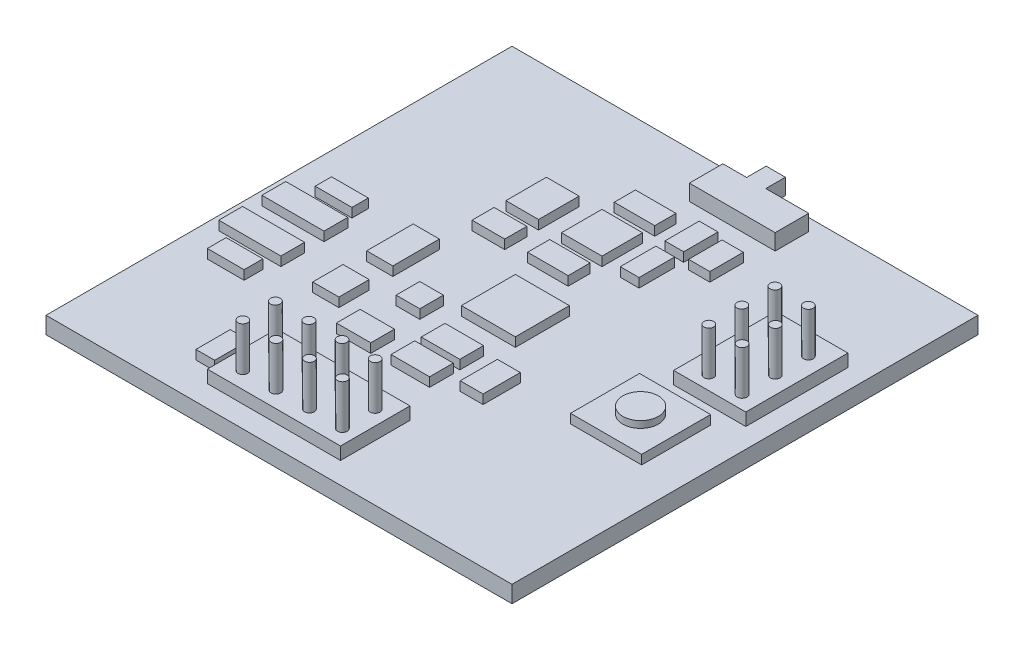
SolidWorks part; units mm, degrees
ref_plane "Front Plane" through (0, 0, 0) normal (0, 0, 1) x (1, 0, 0)
ref_plane "Top Plane" through (0, 0, 0) normal (0, 1, 0) x (1, 0, 0)
ref_plane "Right Plane" through (0, 0, 0) normal (1, 0, 0) x (0, 0, -1)
sketch "Sketch1" plane through (0, 0, 0) normal (0, 1, 0) x (1, 0, 0)
  line L1 (0, 0) -> (35.052, 0)
  line L2 (0, 0) -> (0, 35.052)
  line L3 (0, 35.052) -> (35.052, 35.052)
  line L4 (35.052, 0) -> (35.052, 35.052)
extrude "Boss-Extrude1" add sketch "Sketch1" along normal blind 1.27
sketch "Sketch2" plane through (0, 1.27, 0) normal (0, 1, 0) x (1, 0, 0)
  line L1 (12.548, 13.7882) -> (14.326, 13.7882)
  line L2 (12.548, 13.7882) -> (12.548, 15.5662)
  line L3 (12.548, 15.5662) -> (14.326, 15.5662)
  line L4 (14.326, 13.7882) -> (14.326, 15.5662)
  line L5 (15.6823, 15.5583) -> (19.7463, 15.5583)
  line L6 (15.6823, 15.5583) -> (15.6823, 19.6223)
  line L7 (15.6823, 19.6223) -> (19.7463, 19.6223)
  line L8 (19.7463, 15.5583) -> (19.7463, 19.6223)
  line L9 (14.699, 24.072) -> (17.747, 24.072)
  line L10 (14.699, 24.072) -> (14.699, 27.12)
  line L11 (14.699, 27.12) -> (17.747, 27.12)
  line L12 (17.747, 24.072) -> (17.747, 27.12)
  line L13 (16.7885, 31.6063) -> (23.2414, 31.6063)
  line L14 (16.7885, 31.6063) -> (16.7885, 34.126)
  line L15 (16.7885, 34.126) -> (23.2414, 34.126)
  line L16 (23.2414, 31.6063) -> (23.2414, 34.126)
  line L17 (18.5708, 34.126) -> (20.015, 34.126)
  line L18 (18.5708, 34.126) -> (18.5708, 35.601)
  line L19 (18.5708, 35.601) -> (20.015, 35.601)
  line L20 (20.015, 34.126) -> (20.015, 35.601)
  line L21 (10.52, 27.12) -> (12.9782, 27.12)
  line L22 (10.52, 27.12) -> (10.52, 24.072)
  line L23 (10.52, 24.072) -> (12.9782, 24.072)
  line L24 (12.9782, 27.12) -> (12.9782, 24.072)
  line L25 (14.699, 29.6397) -> (17.747, 29.6397)
  line L26 (14.699, 29.6397) -> (14.699, 28.0419)
  line L27 (14.699, 28.0419) -> (17.747, 28.0419)
  line L28 (17.747, 29.6397) -> (17.747, 28.0419)
  line L29 (21.2134, 29.6397) -> (22.8113, 29.6397)
  line L30 (21.2134, 29.6397) -> (21.2134, 27.12)
  line L31 (21.2134, 27.12) -> (22.8113, 27.12)
  line L32 (22.8113, 29.6397) -> (22.8113, 27.12)
  line L33 (19.1239, 30.0085) -> (20.5374, 30.0085)
  line L34 (19.1239, 30.0085) -> (19.1239, 27.4273)
  line L35 (19.1239, 27.4273) -> (20.5374, 27.4273)
  line L36 (20.5374, 30.0085) -> (20.5374, 27.4273)
  line L37 (19.1239, 26.7513) -> (20.5374, 26.7513)
  line L38 (19.1239, 26.7513) -> (19.1239, 24.072)
  line L39 (19.1239, 24.072) -> (20.5374, 24.072)
  line L40 (20.5374, 26.7513) -> (20.5374, 24.072)
  line L41 (10.52, 23.1868) -> (12.9782, 23.1868)
  line L42 (10.52, 23.1868) -> (10.52, 21.5275)
  line L43 (10.52, 21.5275) -> (12.9782, 21.5275)
  line L44 (12.9782, 23.1868) -> (12.9782, 21.5275)
  line L45 (14.699, 23.1868) -> (17.747, 23.1868)
  line L46 (14.699, 23.1868) -> (14.699, 21.5275)
  line L47 (14.699, 21.5275) -> (17.747, 21.5275)
  line L48 (17.747, 23.1868) -> (17.747, 21.5275)
  line L49 (8.5534, 19.0692) -> (10.52, 19.0692)
  line L50 (8.5534, 19.0692) -> (8.5534, 15.5662)
  line L51 (8.5534, 15.5662) -> (10.52, 15.5662)
  line L52 (10.52, 19.0692) -> (10.52, 15.5662)
  line L53 (8.5534, 13.7882) -> (10.52, 13.7882)
  line L54 (8.5534, 13.7882) -> (8.5534, 11.5101)
  line L55 (8.5534, 11.5101) -> (10.52, 11.5101)
  line L56 (10.52, 13.7882) -> (10.52, 11.5101)
  line L57 (12.1178, 11.5101) -> (14.699, 11.5101)
  line L58 (12.1178, 11.5101) -> (12.1178, 9.7279)
  line L59 (12.1178, 9.7279) -> (14.699, 9.7279)
  line L60 (14.699, 11.5101) -> (14.699, 9.7279)
  line L61 (16.223, 13.7882) -> (19.1239, 13.7882)
  line L62 (16.223, 13.7882) -> (16.223, 12.0017)
  line L63 (16.223, 12.0017) -> (19.1239, 12.0017)
  line L64 (19.1239, 13.7882) -> (19.1239, 12.0017)
  line L65 (16.223, 11.5101) -> (19.1239, 11.5101)
  line L66 (16.223, 11.5101) -> (16.223, 9.7279)
  line L67 (16.223, 9.7279) -> (19.1239, 9.7279)
  line L68 (19.1239, 11.5101) -> (19.1239, 9.7279)
  line L69 (20.5374, 13.4152) -> (22.2581, 13.4152)
  line L70 (20.5374, 13.4152) -> (20.5374, 10.619)
  line L71 (20.5374, 10.619) -> (22.2581, 10.619)
  line L72 (22.2581, 13.4152) -> (22.2581, 10.619)
  line L73 (26.8059, 17.8401) -> (32.1526, 17.8401)
  line L74 (26.8059, 17.8401) -> (26.8059, 12.6492)
  line L75 (26.8059, 12.6492) -> (32.1526, 12.6492)
  line L76 (32.1526, 17.8401) -> (32.1526, 12.6492)
  line L77 (0.9942, 17.0412) -> (5.6649, 17.0412)
  line L78 (0.9942, 17.0412) -> (0.9942, 15.2446)
  line L79 (0.9942, 15.2446) -> (5.6649, 15.2446)
  line L80 (5.6649, 17.0412) -> (5.6649, 15.2446)
  line L81 (0.9942, 13.7882) -> (5.6649, 13.7882)
  line L82 (0.9942, 13.7882) -> (0.9942, 12.0017)
  line L83 (0.9942, 12.0017) -> (5.6649, 12.0017)
  line L84 (5.6649, 13.7882) -> (5.6649, 12.0017)
  line L85 (2.4077, 19.0692) -> (5.1733, 19.0692)
  line L86 (2.4077, 19.0692) -> (2.4077, 17.8401)
  line L87 (2.4077, 17.8401) -> (5.1733, 17.8401)
  line L88 (5.1733, 19.0692) -> (5.1733, 17.8401)
  line L89 (2.4077, 11.1414) -> (5.1733, 11.1414)
  line L90 (2.4077, 11.1414) -> (2.4077, 9.7279)
  line L91 (2.4077, 9.7279) -> (5.1733, 9.7279)
  line L92 (5.1733, 11.1414) -> (5.1733, 9.7279)
  line L93 (8.5534, 5.303) -> (9.9669, 5.303)
  line L94 (8.5534, 5.303) -> (8.5534, 2.7218)
  line L95 (8.5534, 2.7218) -> (9.9669, 2.7218)
  line L96 (9.9669, 5.303) -> (9.9669, 2.7218)
  line L97 (28.1416, 26.7513) -> (33.5661, 26.7513)
  line L98 (28.1416, 26.7513) -> (28.1416, 19.0692)
  line L99 (28.1416, 19.0692) -> (33.5661, 19.0692)
  line L100 (33.5661, 26.7513) -> (33.5661, 19.0692)
  line L101 (10.52, 6.8394) -> (20.5374, 6.8394)
  line L102 (10.52, 6.8394) -> (10.52, 1.6156)
  line L103 (10.52, 1.6156) -> (20.5374, 1.6156)
  line L104 (20.5374, 6.8394) -> (20.5374, 1.6156)
  circle A0 centre (29.4793, 15.2446) radius 1.3377
  circle A1 centre (11.9527, 5.303) radius 0.3687
  circle A2 centre (14.4719, 5.303) radius 0.373
  circle A3 centre (16.9634, 5.303) radius 0.3653
  circle A4 centre (19.4549, 5.303) radius 0.3653
  circle A5 centre (19.4688, 2.8252) radius 0.3653
  circle A6 centre (16.9634, 2.8528) radius 0.3653
  circle A7 centre (14.4719, 2.8252) radius 0.3653
  circle A8 centre (11.9527, 2.8528) radius 0.3653
  circle A9 centre (29.7588, 25.0693) radius 0.3653
  circle A10 centre (32.277, 25.0693) radius 0.3653
  circle A11 centre (32.277, 22.5845) radius 0.3653
  circle A12 centre (32.277, 20.083) radius 0.3653
  circle A13 centre (29.7588, 20.0996) radius 0.3653
  circle A14 centre (29.7588, 22.5845) radius 0.3653
  dimension "D1" = 3.048
  dimension "D2" = 3.048
  dimension "D3" = 1.778
  dimension "D4" = 1.778
  dimension "D5" = 4.064
  dimension "D6" = 4.064
extrude "Boss-Extrude2" add sketch "Sketch2" along normal blind 1.1989 separate body contours L15 L16 L13 L14 | L20 L19 L18 L17
extrude "Boss-Extrude3" add sketch "Sketch2<3>" along normal blind 0.6909 contours L28 L25 L26 L27 region at (16.223, 1.27, -28.8408)
sketch "Sketch2<3>" plane through (0, 1.27, 0) normal (0, 1, 0) x (1, 0, 0) same geometry as "Sketch2"
extrude "Boss-Extrude4" add sketch "Sketch2<4>" along normal blind 0.6909 contours L36 L33 L34 L35 | L32 L29 L30 L31 | L40 L37 L38 L39 | L48 L45 L46 L47 | L24 L21 L22 L23 | L9 L12 L11 L10 | L5 L8 L7 L6 | L68 L65 L66 L67 | L72 L69 L70 L71 | L60 L57 L58 L59 | L56 L53 L54 L55 | L52 L49 L50 L51 | L80 L77 L78 L79 | L84 L81 L82 L83 | L92 L89 L90 L91 | L96 L93 L94 L95 | L41 L44 L43 L42 | L61 L64 L63 L62 | L3 L4 L1 L2 | L85 L88 L87 L86 region at (17.7143, 1.27, -17.5903) region at (16.223, 1.27, -25.596) region at (11.7491, 1.27, -25.596) region at (22.0123, 1.27, -28.3799) region at (19.8306, 1.27, -28.7179) region at (19.8306, 1.27, -25.4116) region at (16.223, 1.27, -22.3571) region at (9.5367, 1.27, -17.3177) region at (9.5367, 1.27, -12.6492) region at (13.4084, 1.27, -10.619) region at (17.6734, 1.27, -10.619) region at (21.3978, 1.27, -12.0171) region at (3.3296, 1.27, -16.1429) region at (3.3296, 1.27, -12.895) region at (3.7905, 1.27, -10.4346) region at (9.2601, 1.27, -4.0124)
sketch "Sketch2<4>" plane through (0, 1.27, 0) normal (0, 1, 0) x (1, 0, 0) same geometry as "Sketch2"
sketch "Sketch5"
extrude "Boss-Extrude5" add sketch "Sketch2<5>" along normal blind 4.2469 contours A9 | A10 | A11 | A12 | A13 | A14 | A5 | A4 | A3 | A6 | A2 | A7 | A1 | A8
sketch "Sketch2<5>" plane through (0, 1.27, 0) normal (0, 1, 0) x (1, 0, 0) same geometry as "Sketch2"
extrude "Boss-Extrude6" add sketch "Sketch2<6>" along normal blind 0.9449 contours L100 L97 L98 L99 A14 A13 A12 A11 A10 A9 | L104 L101 L102 L103 A8 A7 A6 A5 A4 A3 A2 A1 region at (30.8433, 1.27, -22.9314) region at (15.517, 1.27, -4.2377)
sketch "Sketch2<6>" plane through (0, 1.27, 0) normal (0, 1, 0) x (1, 0, 0) same geometry as "Sketch2"
extrude "Boss-Extrude7" add sketch "Sketch2<7>" along normal blind 1.1989 contours A0 region at (29.4793, 1.27, -15.2446)
sketch "Sketch2<7>" plane through (0, 1.27, 0) normal (0, 1, 0) x (1, 0, 0) same geometry as "Sketch2"
extrude "Boss-Extrude8" add sketch "Sketch2<8>" along normal blind 0.6909 contours L76 L73 L74 L75 A0 region at (29.4793, 1.27, -17.7656)
sketch "Sketch2<8>" plane through (0, 1.27, 0) normal (0, 1, 0) x (1, 0, 0) same geometry as "Sketch2"
